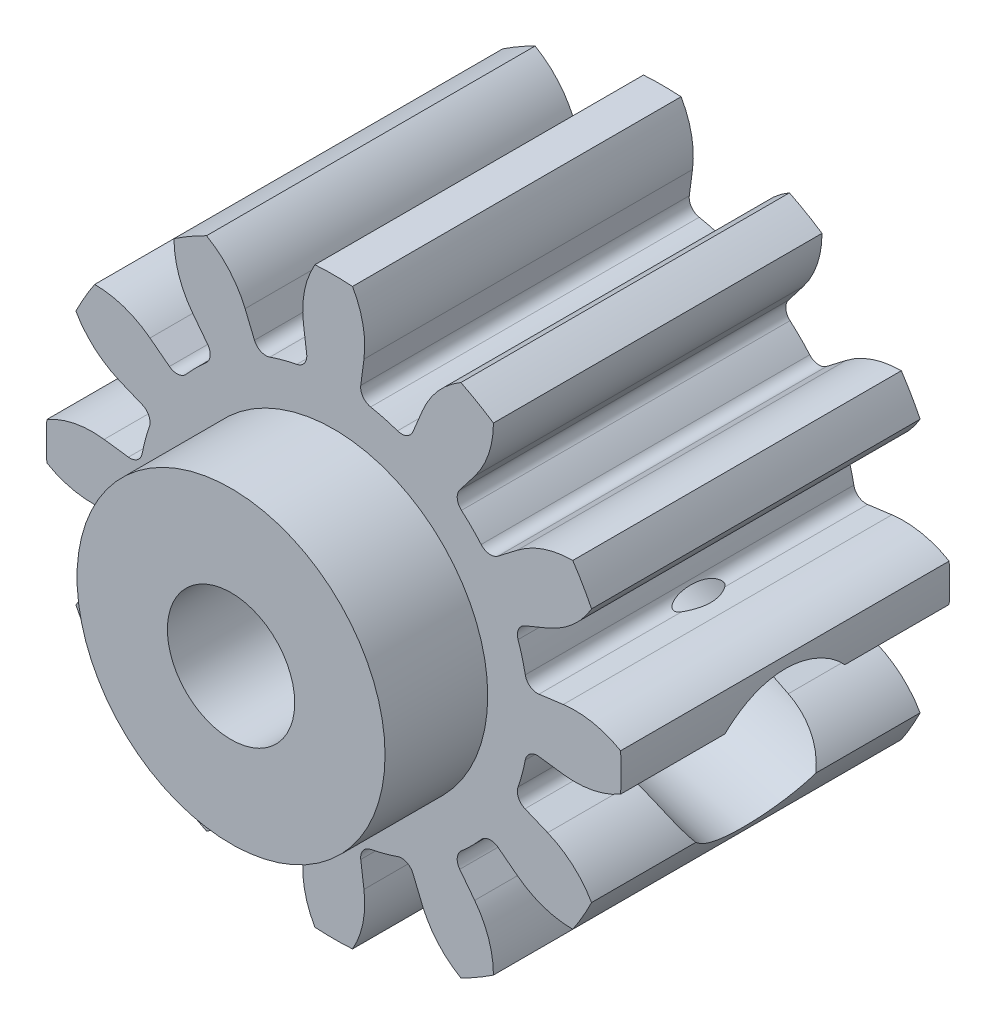
SolidWorks part; units mm, degrees
ref_plane "Front Plane" through (0, 0, 0) normal (0, 0, 1) x (1, 0, 0)
ref_plane "Top Plane" through (0, 0, 0) normal (0, 1, 0) x (1, 0, 0)
ref_plane "Right Plane" through (0, 0, 0) normal (1, 0, 0) x (0, 0, -1)
sketch "Esquisse1" plane through (0, 0, 0) normal (0, 0, 1) x (1, 0, 0)
  line L0 (0, 0) -> (22.1157, 0) construction
  line L1 (0, 0) -> (24.1492, 6.4708) construction
  line L2 (0, 0) -> (24.1492, -6.4708) construction
  line L3 (0, 0) -> (24.9429, 3.2838) construction
  line L4 (0, 0) -> (9.1763, 2.4588)
  line L5 (0, 0) -> (19.7164, -2.5957) construction
  line L6 (0, 0) -> (9.1763, -2.4588)
  line L7 (0, 0) -> (17.7915, 1.1661) construction
  line L8 (9.4187, 1.24) -> (11.1798, 1.4719)
  line L9 (9.4187, -1.24) -> (11.1798, -1.4719)
  line L10 (0, 0) -> (17.695, -1.1598) construction
  circle A0 centre (0, 0) radius 12 construction
  circle A1 centre (0, 0) radius 14 construction
  circle A2 centre (0, 0) radius 9.5 construction
  circle A3 centre (0, 0) radius 11.2763 construction
  arc A4 (9.1763, 2.4588) -> (9.4187, 1.24) centre (0, 0) cw
  arc A5 (9.1763, -2.4588) -> (9.4187, -1.24) centre (0, 0) ccw
  arc A6 (11.1798, 1.4719) -> (13.97, 0.9156) centre (11.7568, -2.9104) cw
  arc A7 (13.97, 0.9156) -> (13.97, -0.9156) centre (0, 0) cw
  arc A8 (11.1798, -1.4719) -> (13.97, -0.9156) centre (11.7568, 2.9104) ccw
  dimension "PrimitiveDiameter" = 24
  dimension "OutsideDiameter" = 28
  dimension "InternalDiameter" = 19
  dimension "BaseDiameter" = 22.5526
  dimension "DemiToothAngle" = 15
  dimension "QuartToothAngle" = 7.5
  dimension "D1" = 7.5
  dimension "D2" = 3.75
  dimension "D3" = 3.75
extrude "MainGear" add sketch "Esquisse1" along normal mid plane 16
fillet "Congé1" radius 0.6 2 edges at (9.4187, -1.24, 0) (9.4187, 1.24, 0)
ref_axis "Axe1" through (0, 0, 8) along (0, 0, -1)
pattern_circular "Répétition circulaire1" count 12 every 30 about axis through (0, 0, 8) along (0, 0, -1) of "MainGear", "Congé1"
sketch "Esquisse3" plane through (0, 0, -8) normal (0, 0, 1) x (1, 0, 0)
  circle A0 centre (0, 0) radius 3.1
  dimension "D1" = 6.2
sketch "Esquisse9" plane through (0, 0, 8) normal (0, 0, 1) x (1, 0, 0)
  circle A0 centre (0, 0) radius 7.5
  circle A2 centre (0, 0) radius 3.1
  dimension "D1" = 6.2
  dimension "D2" = 15
extrude "GearBottomFix" add sketch "Esquisse9" along normal blind 5
extrude "GearHole" cut sketch "Esquisse3" along normal through all
ref_plane "Plane1" through (0, 0, 0) normal (0.9659, -0.2588, 0) x (0, 0, -1)
sketch "Sketch1" plane through (0, 0, 0) normal (0.9659, -0.2588, 0) x (0, 0, -1)
  circle A0 centre (0, 0) radius 1.25
  dimension "D1" = 2.5
extrude "Cut-Extrude2" cut sketch "Sketch1" along normal through all both and the other way through all
ref_plane "Plane2" through (9.1529, -2.4525, 0) normal (0.9659, -0.2588, 0) x (0, 0, -1)
ref_plane "Plane3" through (5.2892, -1.4172, 0) normal (0.9659, -0.2588, 0) x (0, 0, -1)
sketch "Sketch2" plane through (5.2892, -1.4172, 0) normal (0.9659, -0.2588, 0) x (0, 0, -1)
  circle A0 centre (0, 0) radius 4
  dimension "D1" = 8
extrude "Cut-Extrude3" cut sketch "Sketch2" along normal through all
equation "\"Modulo\" = 2"
equation "\"ToothCount\" = 12"
equation "\"PrimitiveDiameter@Esquisse1\"= \"Modulo\" * \"ToothCount\""
equation "\"OutsideDiameter@Esquisse1\" = \"Modulo\" *  ( \"ToothCount\" + 2 ) "
equation "\"InternalDiameter@Esquisse1\" = \"PrimitiveDiameter@Esquisse1\" - \"Modulo\" * 2.5"
equation "\"Angle\"= 20deg"
equation "\"BaseDiameter@Esquisse1\" = \"PrimitiveDiameter@Esquisse1\" * cos ( \"Angle\" ) "
equation "\"DemiToothAngle@Esquisse1\" = 180 / \"ToothCount\""
equation "\"QuartToothAngle@Esquisse1\"= \"DemiToothAngle@Esquisse1\" / 2"
equation "\"D1@Esquisse1\"= \"QuartToothAngle@Esquisse1\""
equation "\"D2@Esquisse1\"= \"QuartToothAngle@Esquisse1\" / 2"
equation "\"D3@Esquisse1\"= \"D2@Esquisse1\""
equation "\"D2@Répétition circulaire1\"=360/\"ToothCount\""
equation "\"D1@Congé1\"=\"Modulo\"*0.3"
